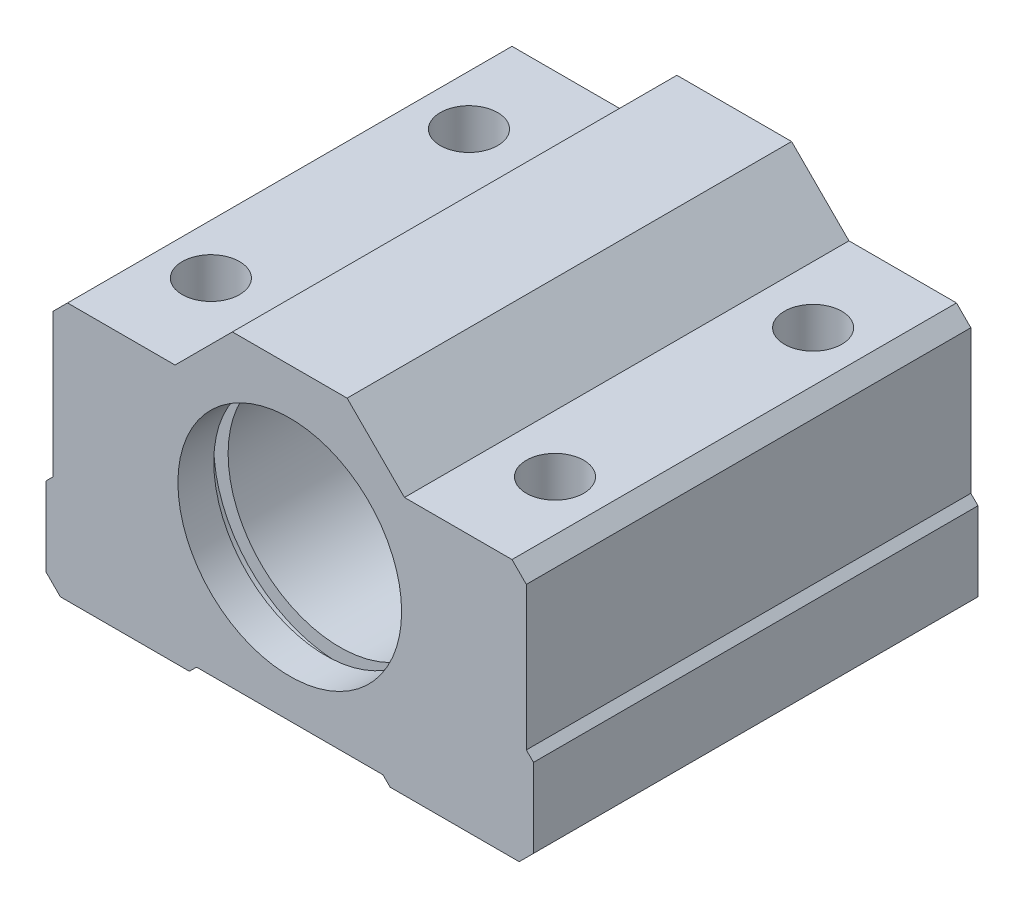
SolidWorks part; units mm, degrees
ref_plane "Front Plane" through (0, 0, 0) normal (0, 0, 1) x (1, 0, 0)
ref_plane "Top Plane" through (0, 0, 0) normal (0, 1, 0) x (1, 0, 0)
ref_plane "Right Plane" through (0, 0, 0) normal (1, 0, 0) x (0, 0, -1)
sketch "Sketch1" plane through (0, 0, 0) normal (0, 0, 1) x (1, 0, 0)
  line L0 (0, 13.5747) -> (0, -13.6751) construction
  line L1 (-16.5, 2.5689) -> (19.4875, 2.5689) construction
  line L2 (-6, -7.9311) -> (6, -7.9311)
  line L3 (6, -7.9311) -> (6, -8.4311)
  line L4 (6, -8.4311) -> (17, -8.4311)
  line L5 (17, -8.4311) -> (17, -0.9311)
  line L6 (17, -0.9311) -> (16.5, -0.9311)
  line L7 (16.5, -0.9311) -> (16.5, 9.5689)
  line L8 (16.5, 9.5689) -> (8, 9.5689)
  line L9 (8, 9.5689) -> (4, 13.5689)
  line L10 (4, 13.5689) -> (-4, 13.5689)
  line L11 (-4, 13.5689) -> (-8, 9.5689)
  line L12 (-8, 9.5689) -> (-16.5, 9.5689)
  line L13 (-16.5, 9.5689) -> (-16.5, -0.9311)
  line L14 (-16.5, -0.9311) -> (-17, -0.9311)
  line L15 (-17, -0.9311) -> (-17, -8.4311)
  line L16 (-17, -8.4311) -> (-6, -8.4311)
  line L17 (-6, -8.4311) -> (-6, -7.9311)
  circle A0 centre (0, 2.5689) radius 7.8
  dimension "D9" = 4
  dimension "D11" = 15.6
  dimension "D12" = 11
  dimension "D23" = 16.5
  dimension "D2" = 8
  dimension "D3" = 4
  dimension "D4" = 21.5
  dimension "D5" = 33
  dimension "D6" = 16.5
  dimension "D7" = 8.5
  dimension "D8" = 8.5
  dimension "D10" = 4
  dimension "D13" = 18
  dimension "D14" = 18
  dimension "D15" = 0.5
  dimension "D16" = 0.5
  dimension "D17" = 12
  dimension "D18" = 6
  dimension "D19" = 34
  dimension "D20" = 17
  dimension "D21" = 7.5
  dimension "D22" = 7.5
extrude "Boss-Extrude1" add sketch "Sketch1" along normal blind 31
chamfer "Chamfer1" distance 1 angle 45 2 edges at (16.5, 9.5689, 15.5) (-16.5, 9.5689, 15.5)
chamfer "Chamfer2" distance 1 angle 45 2 edges at (-17, -0.9311, 15.5) (17, -0.9311, 15.5)
chamfer "Chamfer3" distance 1 angle 45 2 edges at (17, -8.4311, 15.5) (-17, -8.4311, 15.5)
chamfer "Chamfer4" distance 1 angle 45 2 edges at (-6, -8.4311, 15.5) (6, -8.4311, 15.5)
sketch "Sketch2" plane through (0, -8.4311, 0) normal (0, -1, 0) x (1, 0, 0)
  line L0 (-12, 0) -> (-12, 31) construction
  line L1 (-16, 0) -> (-7, 0) construction
  line L2 (-16, 31) -> (-7, 31) construction
  line L3 (12, 0) -> (12, 31) construction
  line L4 (7, 0) -> (16, 0) construction
  line L5 (7, 31) -> (16, 31) construction
  line L6 (-6.5, 0) -> (6.5, 0) construction
  line L7 (-16, 6.5) -> (16, 6.5) construction
  line L8 (-16, 31) -> (-16, 0) construction
  line L9 (16, 0) -> (16, 31) construction
  line L10 (-16, 24.5) -> (16, 24.5) construction
  circle A0 centre (-12, 6.5) radius 2
  circle A1 centre (-12, 24.5) radius 2
  circle A2 centre (12, 6.5) radius 2
  circle A3 centre (12, 24.5) radius 2
  point P12 (0, 0)
  point P15 (0, 0)
  dimension "D5" = 4
  dimension "D6" = 4
  dimension "D7" = 4
  dimension "D8" = 4
  dimension "D1" = 12
  dimension "D2" = 12
  dimension "D3" = 6.5
  dimension "D4" = 6.5
extrude "Cut-Extrude1" cut sketch "Sketch2" against normal up to surface (18 mm away) up to face at (-11.75, 9.5689, 15.5)
sketch "Sketch3" plane through (0, 0, 31) normal (0, 0, 1) x (1, 0, 0)
  circle A0 centre (0, 2.5689) radius 8.8
  dimension "D1" = 17.6
extrude "Cut-Extrude2" cut sketch "Sketch3" against normal blind 3.5
sketch "Sketch4" plane through (0, 0, 0) normal (0, 0, -1) x (-1, 0, 0)
  circle A0 centre (0, 2.5689) radius 8.8
  dimension "D1" = 17.6
extrude "Cut-Extrude3" cut sketch "Sketch4" against normal blind 3.5
sketch "Sketch5" plane through (0, 0, 0) normal (0, 0, -1) x (-1, 0, 0)
  circle A0 centre (0, 2.5689) radius 8.8
  circle A1 centre (0, 2.5689) radius 7.8
  dimension "D1" = 17.6
  dimension "D2" = 15.6
extrude "Boss-Extrude2" add sketch "Sketch5" against normal blind 2.5
sketch "Sketch6" plane through (0, 0, 31) normal (0, 0, 1) x (1, 0, 0)
  circle A0 centre (0, 2.5689) radius 8.8
  circle A1 centre (0, 2.5689) radius 7.8
  dimension "D1" = 17.6
  dimension "D2" = 15.6
extrude "Boss-Extrude3" add sketch "Sketch6" against normal blind 2.5
